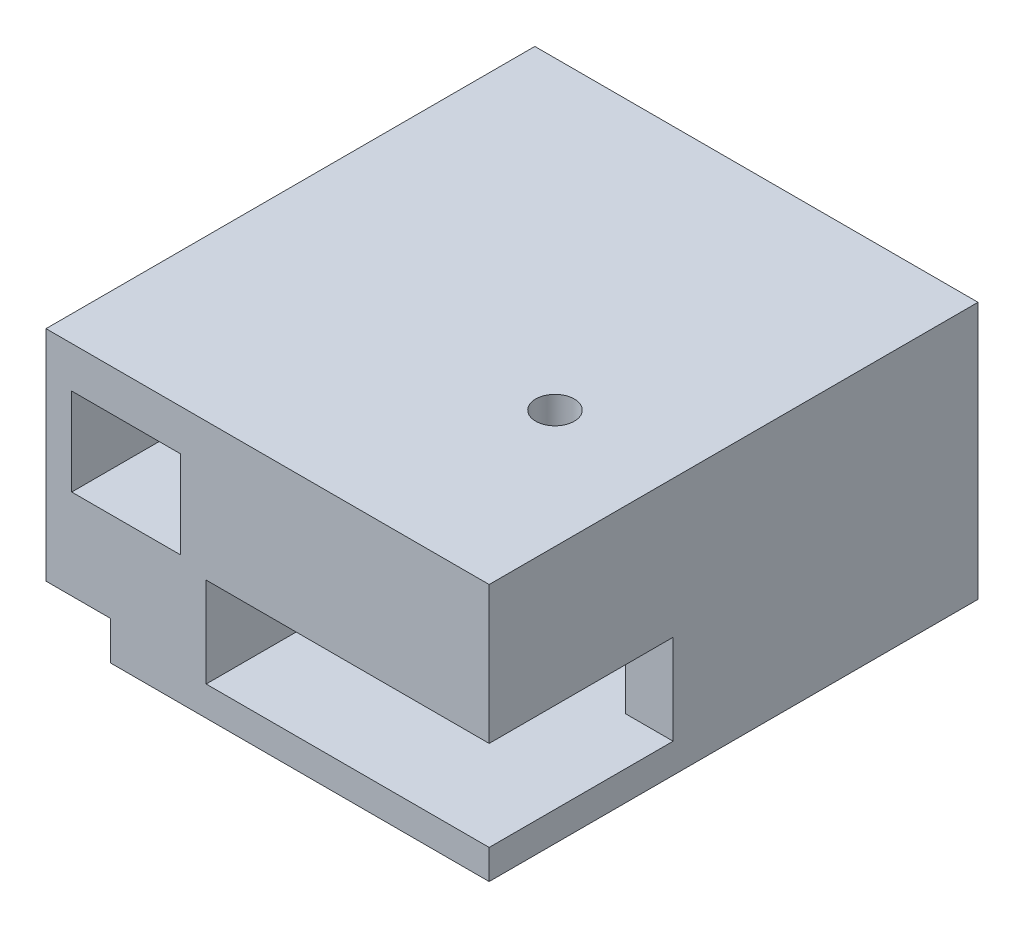
SolidWorks part; units mm, degrees
note: The reader was unsure of these and kept them because the rebuilt part matched: shared geometry of "Sketch1<6>", "Sketch1<7>", "Sketch9<3>", "Sketch6<3>".
ref_plane "Front Plane" through (0, 0, 0) normal (0, 0, 1) x (1, 0, 0)
ref_plane "Top Plane" through (0, 0, 0) normal (0, 1, 0) x (1, 0, 0)
ref_plane "Right Plane" through (0, 0, 0) normal (1, 0, 0) x (0, 0, -1)
sketch "Sketch1" plane through (0, 0, 0) normal (0, 0, 1) x (1, 0, 0)
  line L0 (-16.625, -3.3) -> (-14.825, -3.3)
  line L2 (16.625, 5) -> (16.625, -5)
  line L3 (16.625, -5) -> (-16.625, -5)
  line L4 (-16.625, -3.3) -> (-16.625, -5)
  line L5 (16.625, 5) -> (-16.625, -5) construction
  line L6 (16.625, -5) -> (-16.625, 5) construction
  line L7 (-14.825, -3.3) -> (-14.825, 5)
  line L8 (-2.375, 5) -> (-2.375, -5)
  line L9 (-14.825, -3.3) -> (-14.825, -5)
  line L10 (-14.825, -5) -> (-14.825, -2)
  line L11 (-14.825, -2) -> (-9.825, -2)
  line L12 (-9.825, -2) -> (-9.825, -5)
  line L13 (-2.375, 11.8) -> (-2.375, 15)
  line L14 (16.625, -5) -> (-14.825, -5)
  line L15 (16.625, -5) -> (16.625, 15)
  line L16 (16.625, 15) -> (-14.825, 15)
  line L17 (-14.825, -5) -> (-14.825, 15)
  line L18 (0.9, 15) -> (0.9, -5) construction
  line L19 (16.625, 15) -> (-2.375, 15)
  line L20 (16.625, 15) -> (-14.825, 15)
  line L21 (16.625, 15) -> (16.625, 11.8)
  line L22 (-2.375, 11.8) -> (-14.825, 11.8)
  line L23 (-14.825, 15) -> (-14.825, 11.8)
  line L24 (0.9, 11.8) -> (0.9, 15) construction
  line L25 (16.625, 13.4) -> (-14.825, 13.4) construction
  line L26 (-16.625, 5) -> (-14.825, 5) construction
  line L27 (-16.625, 5) -> (-16.625, -3.3) construction
  line L28 (-2.375, 5) -> (-14.825, 5) construction
  line L29 (-2.375, 5) -> (-14.825, 5)
  line L30 (16.625, 15) -> (16.625, 4.3)
  line L31 (16.625, 4.3) -> (-2.375, 4.3)
  line L32 (-2.375, 15) -> (-2.375, 4.3)
  line L33 (7.125, 4.3) -> (7.125, 15) construction
  line L34 (16.625, 9.65) -> (-2.375, 9.65) construction
  line L35 (16.625, -2.7) -> (-2.375, -2.7)
  line L36 (16.625, -2.7) -> (16.625, -5)
  line L37 (16.625, -5) -> (-2.375, -5)
  line L38 (-2.375, -2.7) -> (-2.375, -5)
  line L39 (7.125, -5) -> (7.125, -2.7) construction
  line L40 (16.625, -3.85) -> (-2.375, -3.85) construction
  point P0 (0, 0)
  point P79 (0.9, 13.4)
  point P96 (7.125, 9.65)
  point P97 (7.125, -3.85)
  point P118 (0.9, 5)
  dimension "D1" = 33.25
  dimension "D2" = 7
  dimension "D3" = 1.8
  dimension "D4" = 1.7
  dimension "D5" = 19
  dimension "D6" = 3
  dimension "D7" = 5
  dimension "D8" = 20
  dimension "D9" = 3.2
  dimension "D10" = 2.3
extrude "Boss-Extrude1" add sketch "Sketch1" against normal blind 38
extrude "Boss-Extrude6" add sketch "Sketch1<6>" against normal blind 38
sketch "Sketch1<6>" plane through (0, 0, 0) normal (0, 0, 1) x (1, 0, 0) same geometry as "Sketch1"
extrude "Boss-Extrude7" add sketch "Sketch1<7>" against normal blind 16 contours L12 L11 L7 L9 L3
sketch "Sketch1<7>" plane through (0, 0, 0) normal (0, 0, 1) x (1, 0, 0) same geometry as "Sketch1"
sketch "Sketch4" plane through (16.625, 0, 0) normal (1, 0, 0) x (0, 0, -1)
  line L1 (0, -2.7) -> (38, -2.7)
  line L2 (0, -2.7) -> (0, -5)
  line L3 (0, -5) -> (38, -5)
  line L4 (38, -2.7) -> (38, -5)
  line L5 (19, -5) -> (19, -2.7) construction
  line L6 (0, -3.85) -> (38, -3.85) construction
  line L7 (0, 15) -> (38, 15)
  line L8 (0, 15) -> (0, 4.3)
  line L9 (0, 4.3) -> (38, 4.3)
  line L10 (38, 15) -> (38, 4.3)
  line L11 (19, 4.3) -> (19, 15) construction
  line L12 (0, 9.65) -> (38, 9.65) construction
  point P64 (19, -3.85)
  point P83 (19, 9.65)
extrude "Boss-Extrude8" add sketch "Sketch4" along normal blind 3
sketch "Sketch5" [suppressed] plane through (0, -2.5, 0) normal (0, -1, 0) x (1, 0, 0)
  line L0 (19.625, -18) -> (-2.375, -18) construction
  line L1 (19.625, 0) -> (16.625, 0)
  line L2 (19.625, 0) -> (19.625, -18)
  line L3 (19.625, -18) -> (16.625, -18)
  line L4 (16.625, 0) -> (16.625, -18)
  line L5 (18.125, -18) -> (18.125, 0) construction
  line L6 (19.625, -9) -> (16.625, -9) construction
  point P72 (18.125, -9)
  dimension "D1" = 3
extrude "Boss-Extrude9" [suppressed] add sketch "Sketch5" along normal blind 1.75
sketch "Sketch6" plane through (0, -2.7, 0) normal (0, 1, 0) x (1, 0, 0)
  line L0 (19.625, 38) -> (19.625, 0) construction
  line L1 (19.625, 38) -> (-2.375, 38) construction
  line L3 (10.442, 23.7) -> (19.625, 23.7)
  line L4 (10.442, 23.7) -> (10.442, 38)
  line L5 (10.442, 38) -> (19.625, 38)
  line L6 (19.625, 23.7) -> (19.625, 38)
  line L7 (15.0335, 38) -> (15.0335, 23.7) construction
  line L8 (10.442, 30.85) -> (19.625, 30.85) construction
  circle A0 centre (10.442, 23.7) radius 1.5
  circle A1 centre (10.442, 23.7) radius 5.5
  point P198 (15.0335, 30.85)
  dimension "D1" = 3
  dimension "D4" = 11
  dimension "D2" = 9.183
  dimension "D3" = 14.3
extrude "Cut-Extrude1" cut sketch "Sketch6" against normal up to next and the other way up to surface contours A0 | L3 A0 L4 other way up to face at (2.4, 15, -19)
sketch "Sketch7" plane through (0, 5, 0) normal (0, 1, 0) x (1, 0, 0)
  line L1 (-2.375, 38) -> (-4.375, 38)
  line L2 (-2.375, 38) -> (-2.375, 0)
  line L3 (-2.375, 0) -> (-4.375, 0)
  line L4 (-4.375, 38) -> (-4.375, 0)
  line L5 (-3.375, 0) -> (-3.375, 38) construction
  line L6 (-2.375, 19) -> (-4.375, 19) construction
  line L8 (-14.825, 38) -> (-12.825, 38)
  line L9 (-14.825, 38) -> (-14.825, 0)
  line L10 (-14.825, 0) -> (-12.825, 0)
  line L11 (-12.825, 38) -> (-12.825, 0)
  line L12 (-13.825, 0) -> (-13.825, 38) construction
  line L13 (-14.825, 19) -> (-12.825, 19) construction
  line L15 (-2.375, 38) -> (-2.375, 0) construction
  line L16 (-2.375, 38) -> (-14.825, 38) construction
  line L17 (-2.375, 0) -> (-14.825, 0) construction
  line L18 (-14.825, 38) -> (-14.825, 0) construction
  point P80 (-13.825, 19)
  point P84 (-3.375, 19)
  dimension "D1" = 2
  dimension "D2" = 2
extrude "Boss-Extrude10" add sketch "Sketch7" along normal up to next
sketch "Sketch8" plane through (0, 4.3, 0) normal (0, -1, 0) x (1, 0, 0)
  line L1 (19.625, 0) -> (12.125, 0)
  line L2 (19.625, 0) -> (19.625, -38)
  line L3 (19.625, -38) -> (12.125, -38)
  line L4 (12.125, 0) -> (12.125, -38)
  line L5 (15.875, -38) -> (15.875, 0) construction
  line L6 (19.625, -19) -> (12.125, -19) construction
  line L7 (19.625, -38) -> (-2.375, -38) construction
  line L8 (19.625, 0) -> (-2.375, 0) construction
  line L9 (19.625, 0) -> (19.625, -38) construction
  point P208 (15.875, -19)
  dimension "D1" = 7.5
extrude "Boss-Extrude11" add sketch "Sketch8" along normal up to next
sketch "Sketch9" plane through (-14.825, 0, 0) normal (-1, 0, 0) x (0, 0, 1)
  line L0 (-38, 15) -> (0, 15) construction
  line L1 (-19.5, 9.65) -> (-24.0401, 9.31) construction
  line L2 (0, -5) -> (0, 15) construction
  line L3 (-24.0401, 9.31) -> (-20.7259, 4.1219) construction
  line L4 (-19.5, 9.65) -> (-5.5, 9.65) construction
  line L5 (-5.5, 9.65) -> (-5.5, 4.1219) construction
  line L6 (-5.5, 4.1219) -> (-20.7259, 4.1219) construction
  line L9 (-23.5, 9.3505) -> (-23.5, 8.4646) construction
  line L10 (-9.5, 6.0191) -> (-9.5, 7.4809)
  line L11 (-5.5, 6.75) -> (-10.3566, 6.75) construction
  line L12 (-10.4597, 6.75) -> (-8.5403, 6.75) construction
  circle A0 centre (-5.5, 6.75) radius 1.5
  circle A1 centre (-19.5, 6.75) radius 1.5 construction
  circle A2 centre (-19.5, 6.75) radius 2.9 construction
  circle A3 centre (-5.5, 6.75) radius 2.9
  point P26 (-9.5, 6.75)
  dimension "D1" = 3
  dimension "D2" = 8.25
  dimension "D4" = 3
  dimension "D6" = 5.8
  dimension "D7" = 5.8
  dimension "D3" = 5.5
  dimension "D5" = 14
  dimension "D8" = 3.3141
  dimension "D10" = 1.2259
  dimension "D11" = 4
  dimension "D12" = 4
extrude "Cut-Extrude2" cut sketch "Sketch9" against normal up to next contours A1 | A0
extrude "Cut-Extrude3" cut sketch "Sketch9<3>" along direction (1, 0, 0) on the side against the normal up to surface (8.45 mm away) from vertex at -2 contours A1 | A2 A1 | A2 L1 L3 | A3 A0 | A0
sketch "Sketch9<3>" plane through (-14.825, 0, 0) normal (-1, 0, 0) x (0, 0, 1) same geometry as "Sketch9"
extrude "Cut-Extrude4" cut sketch "Sketch6<3>" along normal up to surface (7 mm away)
sketch "Sketch6<3>" plane through (0, -2.7, 0) normal (0, 1, 0) x (1, 0, 0) same geometry as "Sketch6"
mirror "Mirror2" about plane through (0, 0, 0) normal (0, 0, 1) of bodies 129
delete or keep bodies "Body-Delete/Keep 1" type delete bodies bodies 129
